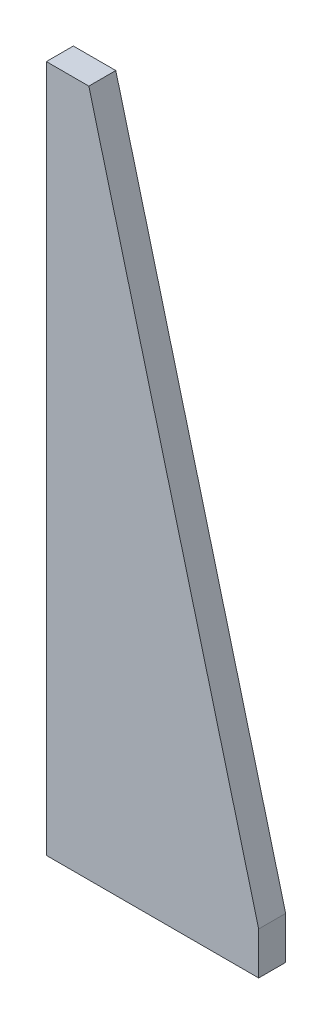
SolidWorks part; units mm, degrees
material "AISI 1020"
ref_plane "Plano frontal" through (0, 0, 0) normal (0, 0, 1) x (1, 0, 0)
ref_plane "Plano superior" through (0, 0, 0) normal (0, 1, 0) x (1, 0, 0)
ref_plane "Plano direito" through (0, 0, 0) normal (1, 0, 0) x (0, 0, -1)
sketch "Esboço1" plane through (0, 0, 0) normal (0, 0, 1) x (1, 0, 0)
  line L0 (0, 0) -> (50, 0)
  line L1 (50, 0) -> (50, 10)
  line L2 (50, 10) -> (10, 161.89)
  line L3 (10, 161.89) -> (0, 161.89)
  line L4 (0, 161.89) -> (0, 0)
  point P3 (0, 0)
  point P7 (0, 0)
  dimension "D1" = 50
  dimension "D2" = 161.89
  dimension "D3" = 10
  dimension "D4" = 10
base flange "Flange-base1" sketch "Esboço1" thickness 6.35 reverse thickness direction no parameters "D1"=0.7366
sketch "Curva-Linhas1" [suppressed] plane through (0, 0, 0) normal (0, 1, 0) x (1, 0, 0)
sketch "Caixa delimitadora1" [suppressed] plane through (0, 0, 0) normal (0, 1, 0) x (1, 0, 0)
sheet metal parameters "Chapa metálica1" thickness 6.35 parameters "D1"=0.7366
flat pattern "Padrão-Plano1" [suppressed]
sketch "Curva-Linhas2" plane through (0, 0, 0) normal (0, 1, 0) x (1, 0, 0)
sketch3d "Caixa delimitadora2" [suppressed]
  line L0 (-50, 161.89, 0) -> (-50, 0, 0) construction
  line L1 (0, 161.89, 0) -> (0, 0, 0) construction
  line L2 (-50, 161.89, 0) -> (0, 161.89, 0) construction
  line L3 (-50, 0, 0) -> (0, 0, 0) construction
